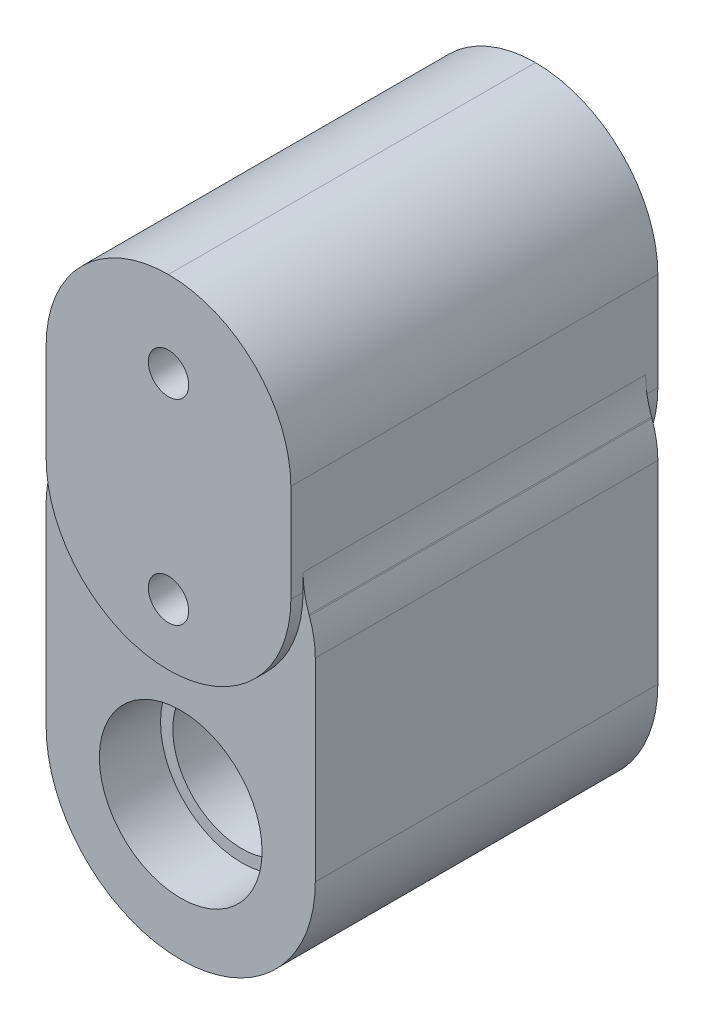
SolidWorks part; units mm, degrees
ref_plane "Спереди" through (0, 0, 0) normal (0, 0, 1) x (1, 0, 0)
ref_plane "Сверху" through (0, 0, 0) normal (0, 1, 0) x (1, 0, 0)
ref_plane "Справа" through (0, 0, 0) normal (1, 0, 0) x (0, 0, -1)
sketch "Эскиз1" plane through (0, 0, 0) normal (0, 0, 1) x (1, 0, 0)
  line L0 (0, 36) -> (0, -11) construction
  line L1 (-11, 38) -> (11, 38)
  line L2 (-11, 38) -> (-11, -11)
  line L3 (-11, -11) -> (11, -11)
  line L4 (11, 38) -> (11, -11)
  line L6 (-11, 0) -> (11, 0) construction
  dimension "D2" = 11
  dimension "D3" = 38
  dimension "D5" = 22
extrude "тело" add sketch "Эскиз1" along normal blind 14 and the other way blind 14
sketch "Эскиз2" plane through (0, 0, 14) normal (0, 0, 1) x (1, 0, 0)
  circle A0 centre (0, 0) radius 6.65
  dimension "D1" = 13.3
extrude "углубление для подшипника" cut sketch "Эскиз2" against normal blind 5
sketch "Эскиз4" plane through (0, 0, 9) normal (0, 0, 1) x (1, 0, 0)
  line L1 (0, 36) -> (0, -11) construction
  line L2 (-11, 0) -> (11, 0) construction
  circle A0 centre (0, 0) radius 5.65
  circle A1 centre (0, 0) radius 6.65 construction
  dimension "D1" = 1
extrude "сквозное отверстие" cut sketch "Эскиз4" against normal through all
mirror "Зеркальное отражение2" about plane through (0, 0, 0) normal (0, 0, 1) of "углубление для подшипника"
fillet "Скругление1" radius 11 2 edges at (11, -11, 0) (-11, -11, 0)
sketch "Эскиз5" plane through (0, 0, -14) normal (0, 0, -1) x (-1, 0, 0)
  line L0 (0, 38) -> (0, -11) construction
  line L1 (-11, 38) -> (11, 38) construction
  circle A0 centre (0, 31) radius 1.65
  circle A1 centre (0, 15) radius 1.65
  circle A2 centre (0, 0) radius 6.65 construction
  dimension "D1" = 3.3
  dimension "D2" = 16
  dimension "D3" = 15
extrude "отверстия под болты" cut sketch "Эскиз5" against normal through all
sketch "Эскиз9" plane through (0, 0, 14) normal (0, 0, 1) x (1, 0, 0)
  line L1 (-11, 10) -> (11, 10) construction
  line L2 (-10, 38) -> (10, 38)
  line L4 (-11, 38) -> (-11, 0) construction
  line L5 (11, 0) -> (11, 38) construction
  line L6 (-10, 20) -> (-10, 38)
  line L9 (10, 38) -> (10, 20)
  line L10 (11, 38) -> (-11, 38) construction
  arc A0 (-10, 20) -> (10, 20) centre (0, 20) ccw
  circle A1 centre (0, 15) radius 1.65
  circle A2 centre (0, 31) radius 1.65
  circle A3 centre (0, 31) radius 1.65 construction
  circle A5 centre (0, 15) radius 1.65 construction
  point P23 (0, 38)
  dimension "D1" = 10
  dimension "D2" = 5
  dimension "D3" = 20
extrude "выступы" add sketch "Эскиз9" along normal blind 1
mirror "Зеркальное отражение1" about plane through (0, 0, 0) normal (0, 0, 1) of "выступы"
sketch "Эскиз10" plane through (0, 0, 14) normal (0, 0, 1) x (1, 0, 0)
  line L0 (-10, 38) -> (-11, 38)
  line L1 (-11, 38) -> (-11, 17.2525)
  line L2 (-11, 38) -> (-11, 0) construction
  line L3 (0, 38) -> (0, 15) construction
  line L4 (-10, 38) -> (-10, 20)
  line L5 (-11, 17.2525) -> (-10, 20)
  line L6 (10, 38) -> (-10, 38) construction
  line L7 (11, 17.2525) -> (10, 20)
  line L8 (10, 38) -> (10, 20)
  line L9 (11, 38) -> (11, 17.2525)
  line L10 (10, 38) -> (11, 38)
  dimension "D1" = 20
extrude "Сглаживание перехода" cut sketch "Эскиз10" against normal up to next
fillet "Скругление2" radius 8 4 edges at (10, 20, 0) (11, 17.2525, 0) (-10, 20, 0) (-11, 17.2525, 0)
fillet "Скругление3" radius 10 2 edges at (-10, 38, 0) (10, 38, 0)
